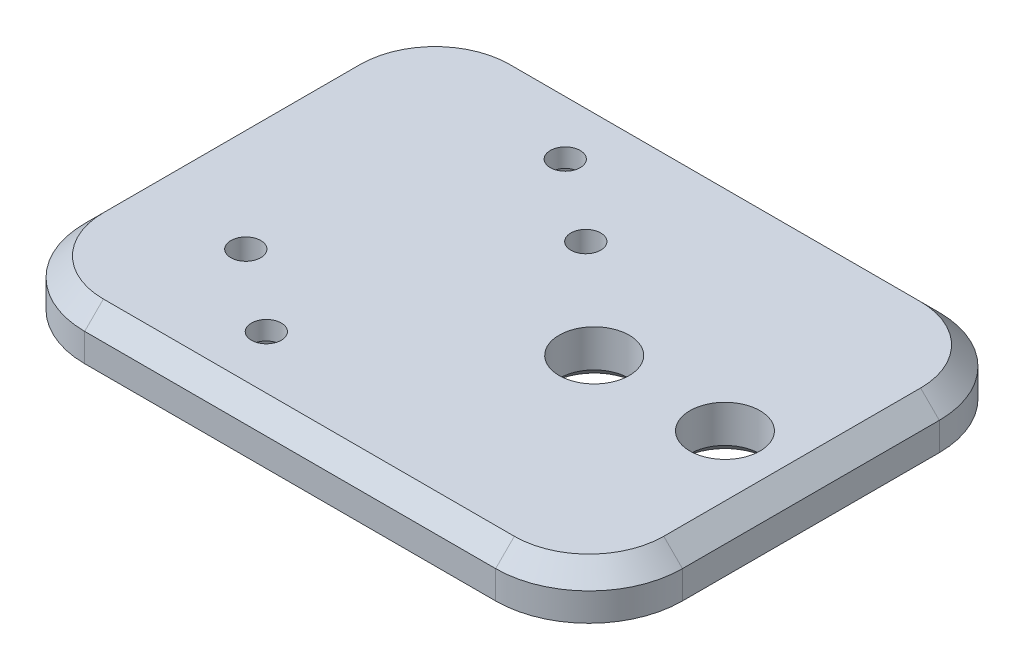
SolidWorks part; units mm, degrees
ref_plane "Front Plane" through (0, 0, 0) normal (0, 0, 1) x (1, 0, 0)
ref_plane "Top Plane" through (0, 0, 0) normal (0, 1, 0) x (1, 0, 0)
ref_plane "Right Plane" through (0, 0, 0) normal (1, 0, 0) x (0, 0, -1)
sketch "Sketch1" plane through (0, 0, 0) normal (0, 1, 0) x (1, 0, 0)
  line L1 (-69.5919, -19.2294) -> (-5.5919, -19.2294)
  line L2 (-69.5919, -19.2294) -> (-69.5919, -66.7294)
  line L3 (-69.5919, -66.7294) -> (-5.5919, -66.7294)
  line L4 (-5.5919, -19.2294) -> (-5.5919, -66.7294)
  line L5 (-69.5919, -19.2294) -> (-5.5919, -66.7294) construction
  line L6 (-69.5919, -66.7294) -> (-5.5919, -19.2294) construction
  line L8 (-59.5919, -19.2294) -> (-15.5919, -19.2294) construction
  line L9 (-5.5919, -29.2294) -> (-5.5919, -66.7294) construction
  circle A0 centre (-39.0919, -33.5794) radius 1.6
  circle A1 centre (-56.5919, -52.4794) radius 1.6
  circle A2 centre (-28.0919, -43.6794) radius 3.75
  circle A3 centre (-14.0919, -43.6794) radius 3.75
  point P0 (0, 0)
  dimension "D1" = 3.2
  dimension "D2" = 3.2
  dimension "D3" = 7.5
  dimension "D4" = 7.5
extrude "Boss-Extrude1" add sketch "Sketch1" along normal blind 5
sketch "Sketch2" plane through (0, 0, 0) normal (0, -1, 0) x (1, 0, 0)
  line L0 (-47.8419, 59.0294) -> (-47.8419, 27.0294) construction
  line L1 (-56.5919, 52.4794) -> (-39.0919, 33.5794) construction
  line L2 (-5.5919, 43.6794) -> (-69.5919, 43.6794) construction
  line L3 (-5.5919, 66.7294) -> (-5.5919, 19.2294) construction
  line L4 (-69.5919, 19.2294) -> (-69.5919, 66.7294) construction
  line L5 (-29.5919, 43.6794) -> (-26.5919, 43.6794) construction
  line L6 (-52.8419, 22.0294) -> (-42.8419, 22.0294) construction
  line L7 (-52.8419, 22.0294) -> (-52.8419, 64.0294) construction
  line L8 (-52.8419, 64.0294) -> (-42.8419, 64.0294) construction
  line L9 (-42.8419, 22.0294) -> (-42.8419, 64.0294) construction
  line L10 (-52.8419, 22.0294) -> (-42.8419, 64.0294) construction
  line L11 (-52.8419, 64.0294) -> (-42.8419, 22.0294) construction
  circle A0 centre (-47.8419, 59.0294) radius 1.6
  circle A3 centre (-47.8419, 27.0294) radius 1.6
  circle A4 centre (-28.0919, 43.6794) radius 1.5 construction
  point P5 (-47.8419, 43.0294)
  point P12 (0, 0)
  point P13 (-25.7209, 22.49)
  dimension "D1" = 3.2
  dimension "D2" = 10
  dimension "D3" = 5
  dimension "D4" = 3.2
  dimension "D5" = 32
extrude "Cut-Extrude1" cut sketch "Sketch2" against normal through all
sketch "Sketch3" plane through (0, 0, 0) normal (0, -1, 0) x (-1, 0, 0)
  line L1 (49.4296, -56.2794) -> (46.2542, -56.2794)
  line L2 (46.2542, -56.2794) -> (44.6665, -59.0294)
  line L3 (44.6665, -59.0294) -> (46.2542, -61.7794)
  line L4 (46.2542, -61.7794) -> (49.4296, -61.7794)
  line L5 (49.4296, -61.7794) -> (51.0173, -59.0294)
  line L6 (51.0173, -59.0294) -> (49.4296, -56.2794)
  line L18 (46.2542, -29.7794) -> (49.4296, -29.7794)
  line L19 (49.4296, -29.7794) -> (51.0173, -27.0294)
  line L20 (51.0173, -27.0294) -> (49.4296, -24.2794)
  line L21 (49.4296, -24.2794) -> (46.2542, -24.2794)
  line L22 (46.2542, -24.2794) -> (44.6665, -27.0294)
  line L23 (44.6665, -27.0294) -> (46.2542, -29.7794)
  line L30 (34.5919, -44.6171) -> (34.5919, -41.4417) [skipped]
  line L31 (34.5919, -41.4417) -> (31.8419, -39.854) [skipped]
  line L32 (31.8419, -39.854) -> (29.0919, -41.4417) [skipped]
  line L33 (29.0919, -41.4417) -> (29.0919, -44.6171) [skipped]
  line L34 (29.0919, -44.6171) -> (31.8419, -46.2048) [skipped]
  line L35 (31.8419, -46.2048) -> (34.5919, -44.6171) [skipped]
  line L36 (61.0919, -41.4417) -> (61.0919, -44.6171) [skipped]
  line L37 (61.0919, -44.6171) -> (63.8419, -46.2048) [skipped]
  line L38 (63.8419, -46.2048) -> (66.5919, -44.6171) [skipped]
  line L39 (66.5919, -44.6171) -> (66.5919, -41.4417) [skipped]
  line L40 (66.5919, -41.4417) -> (63.8419, -39.854) [skipped]
  line L41 (63.8419, -39.854) -> (61.0919, -41.4417) [skipped]
  circle A0 centre (47.8419, -59.0294) radius 2.75 construction
  circle A2 centre (47.8419, -27.0294) radius 2.75 construction
  circle A3 centre (47.8419, -27.0294) radius 1.6 construction
  circle A5 centre (31.8419, -43.0294) radius 2.75 construction
  circle A6 centre (63.8419, -43.0294) radius 2.75 construction
  point P1 (-12.2579, 0.1681)
  point P12 (0, 0)
  point P37 (-1.6784, -9.2773)
  dimension "D2" = 5.5
  dimension "D1" = 4
extrude "Cut-Extrude2" cut sketch "Sketch3" against normal blind 3
fillet "Fillet1" radius 10 2 edges at (-5.5919, 2.5, 19.2294) (-69.5919, 2.5, 19.2294)
fillet "Fillet2" radius 10 2 edges at (-5.5919, 2.5, 66.7294) (-69.5919, 2.5, 66.7294)
chamfer "Chamfer1" distance 2 angle 45 8 edges at (-5.5919, 5, 42.9794) (-69.5919, 5, 42.9794) (-8.5209, 5, 22.1583) (-66.663, 5, 22.1583) (-37.5919, 5, 19.2294) (-37.5919, 5, 66.7294) (-8.5209, 5, 63.8005) (-66.663, 5, 63.8005)
chamfer "Chamfer2" distance 1 angle 45 2 edges at (-28.0919, 0, 47.4294) (-14.0919, 0, 47.4294)
